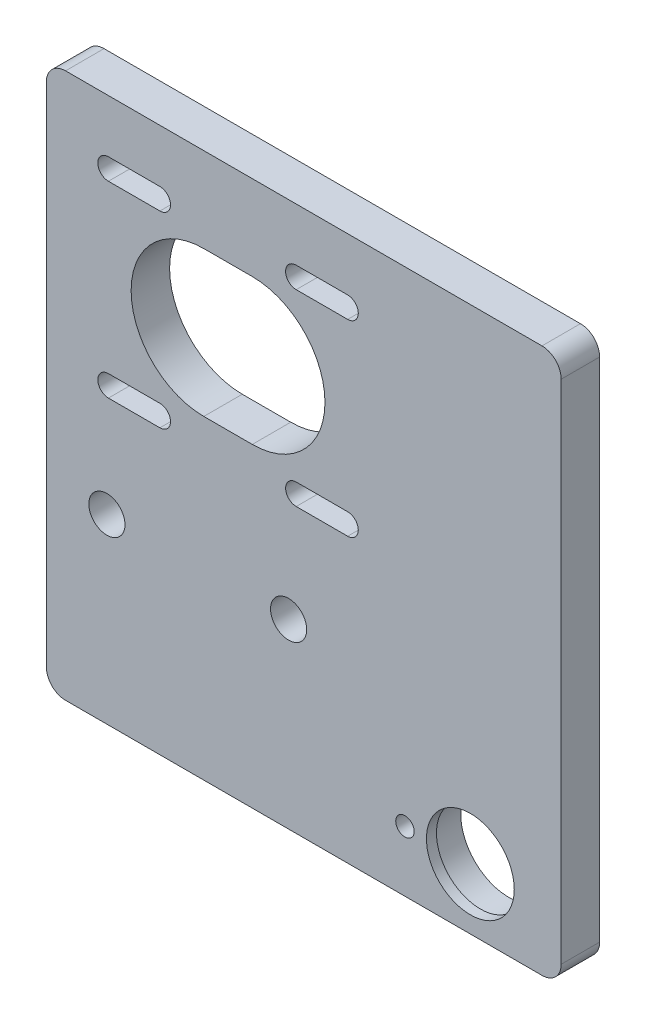
SolidWorks part; units mm, degrees
ref_plane "Front Plane" through (0, 0, 0) normal (0, 0, 1) x (1, 0, 0)
ref_plane "Top Plane" through (0, 0, 0) normal (0, 1, 0) x (1, 0, 0)
ref_plane "Right Plane" through (0, 0, 0) normal (1, 0, 0) x (0, 0, -1)
sketch "Sketch1" plane through (0, 0, 0) normal (0, 0, 1) x (1, 0, 0)
  line L4 (109.4006, 302.2089) -> (109.4006, 218.5589)
  line L10 (194.4006, 218.5589) -> (194.4006, 302.2089)
  line L47 (112.5756, 215.3839) -> (191.2256, 215.3839)
  line L64 (159.1506, 262.1339) -> (150.6506, 262.1339)
  line L65 (119.6506, 262.1339) -> (128.1506, 262.1339)
  line L67 (128.1506, 265.6339) -> (119.6506, 265.6339)
  line L68 (150.6506, 265.6339) -> (159.1506, 265.6339)
  line L69 (135.4006, 267.3839) -> (143.4006, 267.3839)
  line L72 (143.4006, 291.3839) -> (135.4006, 291.3839)
  line L73 (128.1506, 293.1339) -> (119.6506, 293.1339)
  line L74 (150.6506, 293.1339) -> (159.1506, 293.1339)
  line L76 (159.1506, 296.6339) -> (150.6506, 296.6339)
  line L77 (119.6506, 296.6339) -> (128.1506, 296.6339)
  line L79 (191.2256, 305.3839) -> (112.5756, 305.3839)
  circle A14 centre (179.4006, 225.3839) radius 7.9375
  circle A15 centre (179.4006, 225.3839) radius 7.25
  arc A20 (109.4006, 218.5589) -> (112.5756, 215.3839) centre (112.5756, 218.5589) ccw
  arc A21 (191.2256, 215.3839) -> (194.4006, 218.5589) centre (191.2256, 218.5589) ccw
  circle A22 centre (168.6056, 225.3839) radius 1.524
  arc A59 (143.4006, 267.3839) -> (143.4006, 291.3839) centre (143.4006, 279.3839) ccw
  arc A60 (135.4006, 291.3839) -> (135.4006, 267.3839) centre (135.4006, 279.3839) ccw
  arc A64 (194.4006, 302.2089) -> (191.2256, 305.3839) centre (191.2256, 302.2089) ccw
  arc A65 (112.5756, 305.3839) -> (109.4006, 302.2089) centre (112.5756, 302.2089) ccw
  circle A67 centre (149.4006, 245.3839) radius 2.9845
  circle A68 centre (119.4006, 245.3839) radius 2.9845
  arc A71 (150.6506, 296.6339) -> (150.6506, 293.1339) centre (150.6506, 294.8839) ccw
  arc A72 (159.1506, 293.1339) -> (159.1506, 296.6339) centre (159.1506, 294.8839) ccw
  arc A73 (128.1506, 293.1339) -> (128.1506, 296.6339) centre (128.1506, 294.8839) ccw
  arc A74 (119.6506, 296.6339) -> (119.6506, 293.1339) centre (119.6506, 294.8839) ccw
  arc A75 (150.6506, 265.6339) -> (150.6506, 262.1339) centre (150.6506, 263.8839) ccw
  arc A76 (159.1506, 262.1339) -> (159.1506, 265.6339) centre (159.1506, 263.8839) ccw
  arc A77 (128.1506, 262.1339) -> (128.1506, 265.6339) centre (128.1506, 263.8839) ccw
  arc A78 (119.6506, 265.6339) -> (119.6506, 262.1339) centre (119.6506, 263.8839) ccw
extrude "Boss-Extrude1" add sketch "Sketch1" along normal blind 6.35 contours L79 A65 L4 A20 L47 A21 L10 A64 A78 L67 A77 L65 A76 L64 A75 L68 A74 L77 A73 L73 A72 L74 A71 L76 A68 A67 A14 A22 A60 L72 A59 L69 | A14 A15 region at (152.7272, 259.2874, 0) region at (171.6876, 225.3839, 0)
extrude "Cut-Extrude1" cut sketch "Sketch1<3>" along normal blind 4.699 contours A14 A15 region at (171.6876, 225.3839, 0)
sketch "Sketch1<3>" plane through (0, 0, 0) normal (0, 0, 1) x (1, 0, 0) same geometry as "Sketch1"
